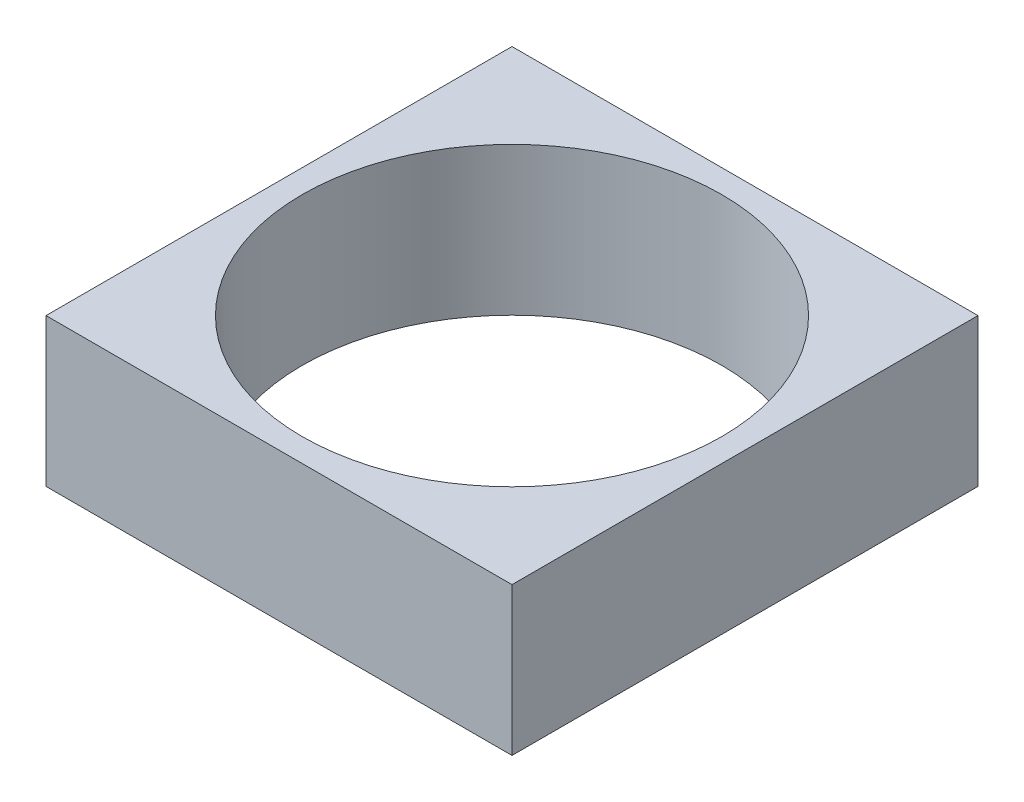
SolidWorks part; units mm, degrees
ref_plane "Front Plane" through (0, 0, 0) normal (0, 0, 1) x (1, 0, 0)
ref_plane "Top Plane" through (0, 0, 0) normal (0, 1, 0) x (1, 0, 0)
ref_plane "Right Plane" through (0, 0, 0) normal (1, 0, 0) x (0, 0, -1)
sketch "Sketch1" plane through (0, 0, 0) normal (0, 1, 0) x (1, 0, 0)
  line L1 (0, 0) -> (10, 0)
  line L2 (0, 0) -> (0, -10)
  line L3 (0, -10) -> (10, -10)
  line L4 (10, 0) -> (10, -10)
  circle A0 centre (5, -5) radius 4.5
  point P8 (5, 0)
  point P10 (0, -5)
  dimension "D3" = 9
  dimension "D1" = 10
  dimension "D2" = 10
extrude "Boss-Extrude1" add sketch "Sketch1" along normal blind 3.175
